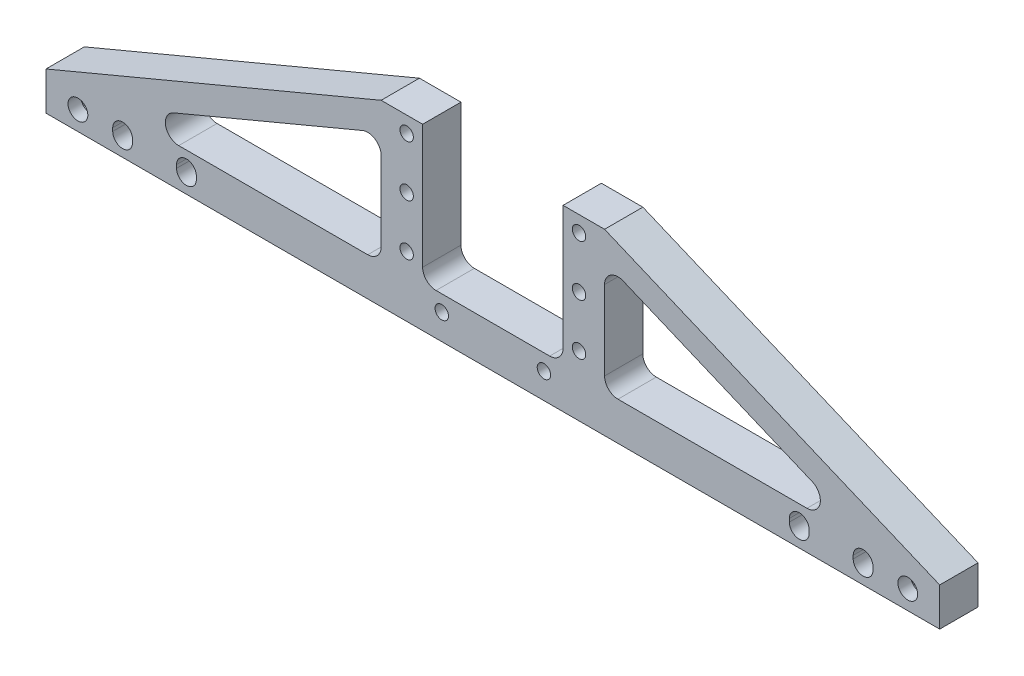
SolidWorks part; units mm, degrees
ref_plane "正面" through (0, 0, 0) normal (0, 0, 1) x (1, 0, 0)
ref_plane "平面" through (0, 0, 0) normal (0, 1, 0) x (1, 0, 0)
ref_plane "右側面" through (0, 0, 0) normal (1, 0, 0) x (0, 0, -1)
sketch "ｽｹｯﾁ1" plane through (0, 0, 0) normal (0, 0, 1) x (1, 0, 0)
  line L0 (-13.5, 21.5) -> (-13.5, 13.5) construction
  line L5 (-13.5, 13.5) -> (-13.5, 5.5) construction
  line L6 (-13.5, 5.5) -> (-13.5, 0) construction
  line L7 (-13.5, 0) -> (-8, 0) construction
  line L8 (-8, 0) -> (8, 0) construction
  line L9 (8, 0) -> (13.5, 0) construction
  line L10 (13.5, 0) -> (13.5, 5.5) construction
  line L11 (13.5, 5.5) -> (13.5, 13.5) construction
  line L12 (13.5, 13.5) -> (13.5, 21.5) construction
  line L13 (-11, 4.6) -> (-11, 24)
  line L14 (-11, 24) -> (-17.5, 24)
  line L15 (-17.5, 24) -> (-17.5, -4) construction
  line L16 (-17.5, -4) -> (17.5, -4)
  line L17 (17.5, -4) -> (17.5, 24) construction
  line L18 (17.5, 24) -> (11, 24)
  line L19 (11, 24) -> (11, 4.6)
  line L20 (8.9, 2.5) -> (-8.9, 2.5)
  line L21 (-17.5, 24) -> (-70, 2)
  line L22 (-70, -4) -> (-17.5, -4)
  line L23 (-17.5, 4.1) -> (-17.5, 16.5061)
  line L24 (-20.4116, 18.4429) -> (-50.017, 6.0368)
  line L25 (-49.2054, 2) -> (-19.6, 2)
  line L26 (-70, 2) -> (-70, -4)
  line L27 (-70, -1) -> (-65, -1) construction
  line L28 (-65, -1) -> (-65, -4) construction
  line L29 (0, -4) -> (0, 24) construction
  line L30 (70, -4) -> (17.5, -4)
  line L31 (70, 2) -> (70, -4)
  line L32 (17.5, 24) -> (70, 2)
  line L33 (20.4116, 18.4429) -> (50.017, 6.0368)
  line L34 (17.5, 4.1) -> (17.5, 16.5061)
  line L35 (49.2054, 2) -> (19.6, 2)
  circle A0 centre (-13.5, 5.5) radius 1.05
  circle A1 centre (-8, 0) radius 1.05
  circle A2 centre (8, 0) radius 1.05
  circle A3 centre (-13.5, 13.5) radius 1.05
  circle A4 centre (-13.5, 21.5) radius 1.05
  circle A5 centre (13.5, 21.5) radius 1.05
  circle A6 centre (13.5, 13.5) radius 1.05
  circle A7 centre (13.5, 5.5) radius 1.05
  arc A8 (-17.5, 4.1) -> (-19.6, 2) centre (-19.6, 4.1) cw
  arc A9 (-50.017, 6.0368) -> (-49.2054, 2) centre (-49.2054, 4.1) ccw
  arc A10 (-17.5, 16.5061) -> (-20.4116, 18.4429) centre (-19.6, 16.5061) ccw
  circle A11 centre (-65, -1) radius 1.55
  circle A12 centre (65, -1) radius 1.55
  arc A13 (17.5, 16.5061) -> (20.4116, 18.4429) centre (19.6, 16.5061) cw
  arc A14 (17.5, 4.1) -> (19.6, 2) centre (19.6, 4.1) ccw
  arc A15 (50.017, 6.0368) -> (49.2054, 2) centre (49.2054, 4.1) cw
  arc A16 (11, 4.6) -> (8.9, 2.5) centre (8.9, 4.6) cw
  arc A17 (-11, 4.6) -> (-8.9, 2.5) centre (-8.9, 4.6) ccw
  point P0 (0, 0)
  point P1 (0, 0)
  point P35 (-17.5, 2)
  point P40 (-17.5, 19.663)
  dimension "D3" = 2.1
  dimension "D15" = 2.1
  dimension "D17" = 3.1
  dimension "D19" = 2.1
  dimension "D1" = 5.5
  dimension "D2" = 8
  dimension "D4" = 27
  dimension "D5" = 2.5
  dimension "D6" = 2.5
  dimension "D7" = 2.5
  dimension "D8" = 4
  dimension "D9" = 4
  dimension "D10" = 2.5
  dimension "D11" = 4
  dimension "D12" = 70
  dimension "D13" = 4
  dimension "D14" = 6
  dimension "D16" = 6
  dimension "D18" = 5
extrude "ﾎﾞｽ - 押し出し1" add sketch "ｽｹｯﾁ1" along normal blind 6
sketch "ｽｹｯﾁ2" plane through (0, 0, 6) normal (0, 0, 1) x (1, 0, 0)
  line L0 (-70, -1) -> (-48, -1) construction
  line L1 (-70, 2) -> (-70, -4) construction
  line L2 (0, -4) -> (0, 2.5) construction
  line L3 (-70, -4) -> (70, -4) construction
  line L4 (8.9, 2.5) -> (-8.9, 2.5) construction
  circle A0 centre (-48, -1) radius 1.55
  circle A1 centre (48, -1) radius 1.55
  circle A2 centre (-58, -1) radius 1.55
  circle A3 centre (58, -1) radius 1.55
  dimension "D1" = 3.1
  dimension "D2" = 22
  dimension "D3" = 10
extrude "ｶｯﾄ - 押し出し1" cut sketch "ｽｹｯﾁ2" against normal blind 3
sketch "ｽｹｯﾁ3" plane through (0, 0, 0) normal (0, 0, -1) x (-1, 0, 0)
  line L0 (-58, -0.75) -> (-58, -1.25) construction
  line L1 (-56.45, -0.75) -> (-56.45, -1.25)
  line L2 (-59.55, -0.75) -> (-59.55, -1.25)
  line L3 (-48, -0.75) -> (-48, -1.25) construction
  line L4 (-46.45, -0.75) -> (-46.45, -1.25)
  line L5 (-49.55, -0.75) -> (-49.55, -1.25)
  line L6 (0, 2.5) -> (0, -4) construction
  line L7 (-8.9, 2.5) -> (8.9, 2.5) construction
  line L8 (70, -4) -> (-70, -4) construction
  line L9 (58, -0.75) -> (58, -1.25) construction
  line L10 (56.45, -0.75) -> (56.45, -1.25)
  line L11 (59.55, -0.75) -> (59.55, -1.25)
  line L12 (48, -0.75) -> (48, -1.25) construction
  line L13 (46.45, -0.75) -> (46.45, -1.25)
  line L14 (49.55, -0.75) -> (49.55, -1.25)
  arc A0 (-56.45, -0.75) -> (-59.55, -0.75) centre (-58, -0.75) ccw
  arc A1 (-59.55, -1.25) -> (-56.45, -1.25) centre (-58, -1.25) ccw
  circle A2 centre (-58, -1) radius 1.55 construction
  arc A3 (-46.45, -0.75) -> (-49.55, -0.75) centre (-48, -0.75) ccw
  arc A4 (-49.55, -1.25) -> (-46.45, -1.25) centre (-48, -1.25) ccw
  arc A5 (56.45, -0.75) -> (59.55, -0.75) centre (58, -0.75) cw
  arc A6 (59.55, -1.25) -> (56.45, -1.25) centre (58, -1.25) cw
  arc A7 (46.45, -0.75) -> (49.55, -0.75) centre (48, -0.75) cw
  arc A8 (49.55, -1.25) -> (46.45, -1.25) centre (48, -1.25) cw
  point P2 (-58, -1)
  point P13 (-48, -1)
  point P25 (58, -1)
  point P32 (48, -1)
  dimension "D1" = 0.5
  dimension "D2" = 2
extrude "ｶｯﾄ - 押し出し2" cut sketch "ｽｹｯﾁ3" against normal through all
sketch "ｽｹｯﾁ4" plane through (0, 0, 0) normal (0, 0, -1) x (-1, 0, 0)
  line L0 (-68, -1) -> (-68, -4)
  line L1 (70, -4) -> (-70, -4) construction
  line L2 (-68, -4) -> (-62, -4)
  line L3 (-62, -4) -> (-62, -1)
  line L4 (0, -4) -> (0, 2.5) construction
  line L5 (-8.9, 2.5) -> (8.9, 2.5) construction
  line L6 (62, -4) -> (62, -1)
  line L7 (68, -4) -> (62, -4)
  line L8 (68, -1) -> (68, -4)
  arc A0 (-62, -1) -> (-68, -1) centre (-65, -1) ccw
  arc A1 (62, -1) -> (68, -1) centre (65, -1) cw
  dimension "D1" = 6
extrude "ｶｯﾄ - 押し出し3" cut sketch "ｽｹｯﾁ4" against normal blind 4
sketch "ｽｹｯﾁ6" plane through (0, 0, 0) normal (0, 0, -1) x (-1, 0, 0)
  line L0 (0, -4) -> (0, 24.1954) construction
  line L1 (62, -4) -> (-62, -4) construction
  circle A0 centre (-13.5, 21.5) radius 1.9
  circle A1 centre (-13.5, 13.5) radius 1.9
  circle A2 centre (-13.5, 5.5) radius 1.9
  circle A3 centre (-8, 0) radius 1.9
  circle A4 centre (8, 0) radius 1.9
  circle A5 centre (13.5, 5.5) radius 1.9
  circle A6 centre (13.5, 13.5) radius 1.9
  circle A7 centre (13.5, 21.5) radius 1.9
  dimension "D1" = 3.8
  dimension "D2" = 3
extrude "ｶｯﾄ - 押し出し4" cut sketch "ｽｹｯﾁ6" against normal blind 3
sketch "ｽｹｯﾁ7" plane through (0, 0, 4) normal (0, 0, -1) x (-1, 0, 0)
  line L0 (68, -4) -> (68, -1) construction
  line L1 (62, -4) -> (68, -4)
  line L2 (62, -4) -> (62, -3.99)
  line L3 (62, -3.99) -> (68, -3.99)
  line L4 (68, -4) -> (68, -3.99)
  line L5 (-62, -4) -> (-62, -1) construction
  line L6 (-68, -4) -> (-62, -4)
  line L7 (-68, -4) -> (-68, -3.99)
  line L8 (-68, -3.99) -> (-62, -3.99)
  line L9 (-62, -4) -> (-62, -3.99)
  dimension "D1" = 0.01
extrude "ﾎﾞｽ - 押し出し2" add sketch "ｽｹｯﾁ7" along normal up to surface (4 mm away) up to face at (-11.6, 21.5, 0)
